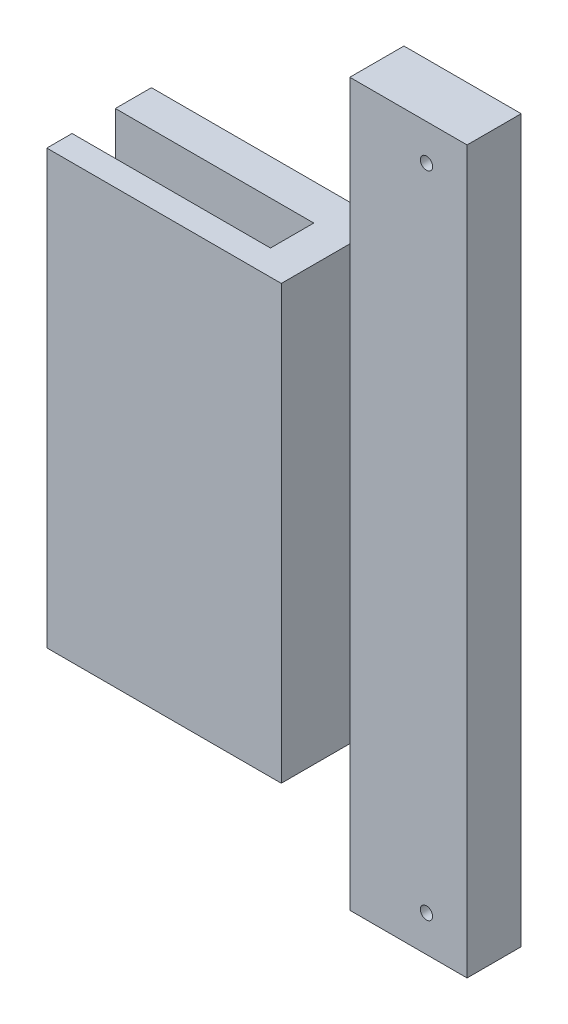
SolidWorks part; units mm, degrees
ref_plane "Front Plane" through (0, 0, 0) normal (1, 0, 0) x (0, 1, 0)
ref_plane "Top Plane" through (0, 0, 0) normal (0, 0, 1) x (0, 1, 0)
ref_plane "Right Plane" through (0, 0, 0) normal (0, 1, 0) x (-1, 0, 0)
sketch "Sketch1" plane through (0, 0, 0) normal (0, 0, 1) x (0, 1, 0)
  line L0 (-100, 11.25) -> (-100, 21.25)
  line L1 (100, -11.25) -> (-100, -11.25)
  line L2 (100, -11.25) -> (100, 11.25)
  line L3 (100, 11.25) -> (-100, 11.25) construction
  line L4 (-100, -11.25) -> (-100, 11.25)
  line L5 (100, -11.25) -> (-100, 11.25) construction
  line L6 (100, 11.25) -> (-100, -11.25) construction
  line L7 (100, 11.25) -> (100, 21.25)
  line L8 (-100, 21.25) -> (100, 21.25)
  point P0 (0, 0)
  dimension "D1" = 200
  dimension "D2" = 22.5
  dimension "D3" = 10
extrude "Boss-Extrude1" add sketch "Sketch1" along normal blind 15
sketch "Sketch2" plane through (0, 0, 15) normal (0, 0, 1) x (1, 0, 0)
  line L0 (0, 50) -> (0, -50) construction
  line L2 (11.5, 72) -> (-11.5, 72)
  line L3 (11.5, 72) -> (11.5, -72)
  line L4 (11.5, -72) -> (-11.5, -72)
  line L5 (-11.5, 72) -> (-11.5, -72)
  line L6 (11.5, 72) -> (-11.5, -72) construction
  line L7 (11.5, -72) -> (-11.5, 72) construction
  circle A0 centre (0, 50) radius 3.15 construction
  circle A1 centre (0, -50) radius 3.15 construction
  point P4 (0, 0)
  point P7 (0, 0)
  dimension "D1" = 6.3
  dimension "D2" = 6.3
  dimension "D5" = 23
  dimension "D3" = 100
  dimension "D4" = 144
sketch "Sketch4" plane through (0, 0, 15) normal (0, 0, 1) x (1, 0, 0)
  line L0 (0, 90) -> (0, -90) construction
  circle A0 centre (0, 90) radius 1.7
  circle A1 centre (0, -90) radius 1.7
  point P4 (0, 0)
  dimension "D1" = 3.4
  dimension "D2" = 3.4
  dimension "D3" = 180
extrude "Cut-Extrude3" cut sketch "Sketch4" against normal blind 15
hole_wizard "CBORE for M3 SBHCS1" positions "3DSketch1" profile "Sketch5" counterbore size "M3" standard "ANSI Metric"
sketch3d "3DSketch1"
  line L0 (0, 90, 0) -> (0, 90, 15) construction
  point P0 (0, 90, 0)
sketch "Sketch5" plane through (0, 90, 0) normal (1, 0, 0) x (0, 1, 0)
  line L0 (0, 0) -> (0, 4.1715)
  line L1 (0, 4.1715) -> (1.7, 3.15)
  line L2 (1.7, 3.15) -> (1.7, 1.65)
  line L3 (1.7, 1.65) -> (3.35, 1.65)
  line L4 (3.35, 1.65) -> (3.35, 0)
  line L5 (3.35, 0) -> (0, 0)
  line L10 (0, 4.1715) -> (-1.7, 3.15) construction
  line L11 (0, -6.35) -> (0, 107.95) construction
  dimension "Hole Dia." = 3.4
  dimension "Hole Depth" = 3.15
  dimension "C'Bore Dia." = 6.7
  dimension "C'Bore Depth" = 1.65
  dimension "Drill Angle" = 118
hole_wizard "CBORE for M3 SBHCS2" positions "3DSketch2" profile "Sketch6" counterbore size "M3" standard "ANSI Metric"
sketch3d "3DSketch2"
  line L0 (0, -90, 0) -> (0, -90, 15) construction
  point P0 (0, -90, 0)
sketch "Sketch6" plane through (0, -90, 0) normal (1, 0, 0) x (0, 1, 0)
  line L0 (0, 0) -> (0, 4.1715)
  line L1 (0, 4.1715) -> (1.7, 3.15)
  line L2 (1.7, 3.15) -> (1.7, 1.65)
  line L3 (1.7, 1.65) -> (3.35, 1.65)
  line L4 (3.35, 1.65) -> (3.35, 0)
  line L5 (3.35, 0) -> (0, 0)
  line L10 (0, 4.1715) -> (-1.7, 3.15) construction
  line L11 (0, -6.35) -> (0, 107.95) construction
  dimension "Hole Dia." = 3.4
  dimension "Hole Depth" = 3.15
  dimension "C'Bore Dia." = 6.7
  dimension "C'Bore Depth" = 1.65
  dimension "Drill Angle" = 118
sketch "Sketch7" plane through (0, 0, 0) normal (0, 0, -1) x (1, 0, 0)
  line L0 (0, 0) -> (-21.25, 0) construction
  line L1 (-21.25, -100) -> (-21.25, 100) construction
  line L2 (-21.25, 60) -> (-21.25, -60)
  line L3 (-21.25, 60) -> (-86.25, 60)
  line L4 (-86.25, 60) -> (-86.25, -60)
  line L5 (-21.25, -60) -> (-86.25, -60)
  point P7 (-21.25, 0)
  dimension "D1" = 65
  dimension "D2" = 120
extrude "Boss-Extrude2" add sketch "Sketch7" against normal blind 15
sketch "Sketch8" plane through (0, 0, 0) normal (0, 0, -1) x (1, 0, 0)
  line L1 (-21.25, 60) -> (-86.25, 60)
  line L2 (-21.25, 60) -> (-21.25, -60)
  line L3 (-21.25, -60) -> (-86.25, -60)
  line L4 (-86.25, 60) -> (-86.25, -60)
extrude "Cut-Extrude4" cut sketch "Sketch8" against normal blind 5
sketch "Sketch9" plane through (0, 0, 15) normal (0, 0, 1) x (1, 0, 0)
  line L0 (-21.25, -60) -> (-86.25, -60) construction
  line L1 (-21.25, 60) -> (-31.25, 60)
  line L2 (-21.25, 60) -> (-21.25, -60)
  line L3 (-21.25, -60) -> (-31.25, -60)
  line L4 (-31.25, 60) -> (-31.25, -60)
  dimension "D1" = 10
extrude "Boss-Extrude3" add sketch "Sketch9" along normal blind 12
sketch "Sketch10" plane through (0, 0, 27) normal (0, 0, 1) x (1, 0, 0)
  line L1 (-21.25, 60) -> (-86.25, 60)
  line L2 (-21.25, 60) -> (-21.25, -60)
  line L3 (-21.25, -60) -> (-86.25, -60)
  line L4 (-86.25, 60) -> (-86.25, -60)
extrude "Boss-Extrude4" add sketch "Sketch10" along normal blind 7
sketch "Sketch11" plane through (0, 0, 27) normal (0, 0, -1) x (1, 0, 0)
  line L0 (-86.25, 60) -> (-86.25, -60) construction
  line L1 (-86.25, -60) -> (-21.25, -60) construction
  circle A0 centre (-62.74, 0) radius 11
  dimension "D1" = 22
  dimension "D2" = 23.51
  dimension "D3" = 60
extrude "Boss-Extrude5" add sketch "Sketch11" along normal blind 12
